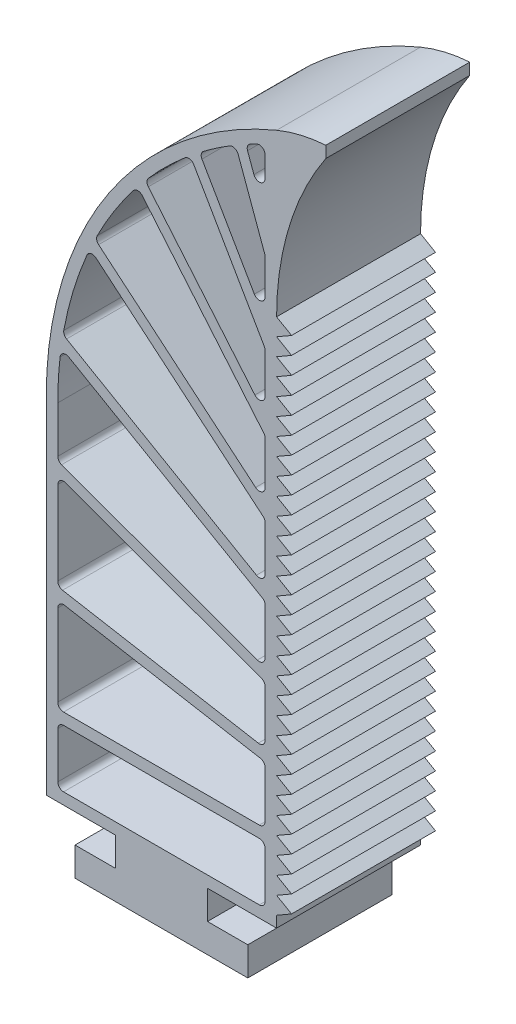
SolidWorks part; units mm, degrees
ref_plane "Front Plane" through (0, 0, 0) normal (0, 0, 1) x (1, 0, 0)
ref_plane "Top Plane" through (0, 0, 0) normal (0, 1, 0) x (1, 0, 0)
ref_plane "Right Plane" through (0, 0, 0) normal (1, 0, 0) x (0, 0, -1)
sketch "Sketch2" plane through (0, 0, 0) normal (0, 0, 1) x (1, 0, 0)
  line L0 (-15, 0) -> (15, 0)
  line L1 (15, 0) -> (15, 5)
  line L2 (15, 5) -> (8, 5)
  line L3 (8, 5) -> (8, 10)
  line L4 (8, 10) -> (20, 10)
  line L5 (20, 10) -> (20, 130)
  line L6 (-15, 0) -> (-15, 5)
  line L7 (-15, 5) -> (-8, 5)
  line L8 (-8, 5) -> (-8, 10)
  line L9 (-8, 10) -> (-20, 10)
  line L10 (-20, 10) -> (-20, 70)
  arc A0 (20, 130) -> (-20, 70) centre (45, 70) ccw
  dimension "D1" = 30
  dimension "D2" = 5
  dimension "D3" = 5
  dimension "D4" = 40
  dimension "D5" = 120
  dimension "D6" = 60
  dimension "D7" = 16
extrude "Boss-Extrude1" add sketch "Sketch2" along normal blind 25
sketch "Sketch3" plane through (0, 0, 25) normal (0, 0, 1) x (1, 0, 0)
  line L0 (-18, 12) -> (18, 12)
  line L1 (18, 12) -> (18, 22)
  line L2 (18, 22) -> (-18, 22)
  line L3 (-18, 22) -> (-18, 12)
  line L4 (-20, 70) -> (-20, 10) construction
  line L5 (20, 10) -> (20, 130) construction
  line L6 (8, 10) -> (20, 10) construction
  dimension "D1" = 2
  dimension "D2" = 2
  dimension "D3" = 2
  dimension "D4" = 10
sketch "Sketch4" plane through (0, 0, 25) normal (0, 0, 1) x (1, 0, 0)
  line L0 (-18, 24) -> (18, 24)
  line L1 (18, 24) -> (18, 34)
  line L2 (18, 34) -> (-18, 40.3478)
  line L3 (-18, 40.3478) -> (-18, 24)
  line L4 (-20, 70) -> (-20, 10) construction
  line L5 (18, 22) -> (-18, 22) construction
  line L6 (20, 10) -> (20, 130) construction
  dimension "D1" = 2
  dimension "D2" = 2
  dimension "D3" = 2
  dimension "D4" = 10
  dimension "D5" = 10
sketch "Sketch5" plane through (0, 0, 25) normal (0, 0, 1) x (1, 0, 0)
  line L0 (-18, 42.3786) -> (18, 36.0309)
  line L1 (18, 36.0309) -> (18, 46.0309)
  line L2 (18, 46.0309) -> (-18, 59.1338)
  line L3 (-18, 59.1338) -> (-18, 42.3786)
  line L4 (-20, 70) -> (-20, 10) construction
  line L5 (20, 10) -> (20, 130) construction
  line L7 (18, 34) -> (-18, 40.3478) construction
  line L8 (-18, 24) -> (18, 24) construction
  dimension "D1" = 2
  dimension "D2" = 2
  dimension "D3" = 2
  dimension "D4" = 20
  dimension "D5" = 10
sketch "Sketch6" plane through (0, 0, 25) normal (0, 0, 1) x (1, 0, 0)
  line L0 (-18, 61.2621) -> (18, 48.1592)
  line L1 (18, 48.1592) -> (18, 58.1592)
  line L2 (18, 58.1592) -> (-17.4098, 78.6031)
  line L3 (-18, 61.2621) -> (-18, 70)
  line L5 (18, 46.0309) -> (-18, 59.1338) construction
  line L6 (-20, 70) -> (-20, 10) construction
  line L7 (20, 10) -> (20, 130) construction
  line L8 (-18, 24) -> (18, 24) construction
  arc A0 (-17.4098, 78.6031) -> (-18, 70) centre (45, 70) ccw
  arc A2 (20, 130) -> (-20, 70) centre (45, 70) ccw construction
  dimension "D1" = 2
  dimension "D2" = 2
  dimension "D3" = 2
  dimension "D4" = 30
  dimension "D5" = 10
extrude "Cut-Extrude1" cut sketch "Sketch3" against normal through all contours L0 L1 L2 L3
extrude "Cut-Extrude2" cut sketch "Sketch4" against normal through all contours L0 L1 L2 L3
extrude "Cut-Extrude3" cut sketch "Sketch5" against normal through all contours L0 L1 L2 L3
extrude "Cut-Extrude4" cut sketch "Sketch6" against normal through all contours L0 L1 L2 A0 L3
sketch "Sketch13" plane through (0, 0, 25) normal (0, 0, 1) x (1, 0, 0)
  line L0 (20, 10) -> (20, 130) construction
  line L1 (28.5436, 132.0151) -> (28.5436, 130.0151)
  line L2 (20, 130) -> (20, 101.9347)
  arc A0 (20, 130) -> (28.5436, 132.0151) centre (30.3921, 105.059) cw
  arc A1 (20, 101.9347) -> (28.5436, 130.0151) centre (70.4182, 101.9347) cw
  arc A2 (20, 130) -> (-20, 70) centre (45, 70) ccw construction
  dimension "D1" = 2
extrude "Boss-Extrude2" add sketch "Sketch13" against normal up to surface (25 mm away) up to face at (-0.7569, 22.1713, 0)
sketch "Sketch15" plane through (0, 0, 25) normal (0, 0, 1) x (1, 0, 0)
  line L0 (20, 101.9347) -> (22.5981, 100.4347)
  line L1 (22.5981, 100.4347) -> (20, 98.9347)
  line L2 (20, 10) -> (20, 101.9347) construction
  line L3 (20, 101.9347) -> (20, 98.9347)
  dimension "D1" = 3
  dimension "D2" = 3
  dimension "D3" = 3
extrude "Boss-Extrude3" add sketch "Sketch15" against normal up to surface (25 mm away) up to face at (4.3889, 42.067, 0)
pattern_linear "LPattern1" count 30 spacing 3 along (0, -1, 0) of "Boss-Extrude3"
sketch "Sketch17" plane through (0, 0, 25) normal (0, 0, 1) x (1, 0, 0)
  line L0 (-17.0808, 80.7225) -> (18, 60.4686)
  line L1 (18, 60.4686) -> (18, 70.4686)
  line L2 (18, 70.4686) -> (-12.3964, 95.9742)
  line L3 (18, 58.1592) -> (-17.4098, 78.6031) construction
  line L4 (18, 48.1592) -> (18, 58.1592) construction
  arc A0 (-12.3964, 95.9742) -> (-17.0808, 80.7225) centre (45, 70) ccw
  arc A1 (-17.4098, 78.6031) -> (-18, 70) centre (45, 70) ccw construction
  dimension "D1" = 10
  dimension "D2" = 2
  dimension "D3" = 10
extrude "Cut-Extrude5" cut sketch "Sketch17" against normal through all contours L2 A0 L0 L1
sketch "Sketch18" plane through (0, 0, 25) normal (0, 0, 1) x (1, 0, 0)
  line L0 (-11.513, 97.8438) -> (18, 73.0794)
  line L1 (18, 73.0794) -> (18, 83.0794)
  line L2 (18, 83.0794) -> (-4.1233, 109.4449)
  line L3 (18, 70.4686) -> (-12.3964, 95.9742) construction
  line L4 (18, 60.4686) -> (18, 70.4686) construction
  arc A0 (-4.1233, 109.4449) -> (-11.513, 97.8438) centre (45, 70) ccw
  arc A1 (-12.3964, 95.9742) -> (-17.0808, 80.7225) centre (45, 70) ccw construction
  dimension "D1" = 2
  dimension "D2" = 10
  dimension "D3" = 10
extrude "Cut-Extrude6" cut sketch "Sketch18" against normal through all
sketch "Sketch19" plane through (0, 0, 25) normal (0, 0, 1) x (1, 0, 0)
  line L0 (-2.8251, 111.0093) -> (18, 86.1909)
  line L1 (18, 86.1909) -> (18, 96.1909)
  line L2 (18, 96.1909) -> (5.0138, 118.6837)
  line L3 (18, 73.0794) -> (18, 83.0794) construction
  line L5 (18, 83.0794) -> (-4.1233, 109.4449) construction
  arc A0 (5.0138, 118.6837) -> (-2.8251, 111.0093) centre (45, 70) ccw
  arc A1 (-4.1233, 109.4449) -> (-11.513, 97.8438) centre (45, 70) ccw construction
  dimension "D1" = 10
  dimension "D2" = 2
  dimension "D3" = 10
extrude "Cut-Extrude7" cut sketch "Sketch19" against normal through all contours L2 A0 L0 L1
sketch "Sketch21" plane through (0, 0, 25) normal (0, 0, 1) x (1, 0, 0)
  line L0 (6.5968, 119.9419) -> (18, 100.1909)
  line L1 (18, 100.1909) -> (18, 110.1909)
  line L2 (18, 110.1909) -> (12.8983, 124.2077)
  line L3 (18, 96.1909) -> (5.0138, 118.6837) construction
  line L4 (18, 86.1909) -> (18, 96.1909) construction
  arc A0 (12.8983, 124.2077) -> (6.5968, 119.9419) centre (45, 70) ccw
  arc A1 (5.0138, 118.6837) -> (-2.8251, 111.0093) centre (45, 70) ccw construction
  dimension "D1" = 10
  dimension "D2" = 2
  dimension "D3" = 10
extrude "Cut-Extrude8" cut sketch "Sketch21" against normal through all
sketch "Sketch22" plane through (0, 0, 25) normal (0, 0, 1) x (1, 0, 0)
  line L0 (14.6606, 125.2134) -> (18, 116.0385)
  line L1 (18, 116.0385) -> (18, 126.921)
  line L2 (18, 110.1909) -> (12.8983, 124.2077) construction
  line L3 (18, 100.1909) -> (18, 110.1909) construction
  arc A0 (18, 126.921) -> (14.6606, 125.2134) centre (45, 70) ccw
  arc A1 (12.8983, 124.2077) -> (6.5968, 119.9419) centre (45, 70) ccw construction
  dimension "D1" = 2
extrude "Cut-Extrude9" cut sketch "Sketch22" against normal through all
fillet "Fillet1" radius 1 35 edges at (18, 126.921, 12.5) (14.6606, 125.2134, 12.5) (6.5968, 119.9419, 12.5) (12.8983, 124.2077, 12.5) (18, 116.0385, 12.5) (18, 100.1909, 12.5) (-2.8251, 111.0093, 12.5) (5.0138, 118.6837, 12.5) (18, 86.1909, 12.5) (18, 73.0794, 12.5) (18, 60.4686, 12.5) (18, 46.0309, 12.5) (18, 22, 12.5) (18, 34, 12.5) (-18, 40.3478, 12.5) (-18, 22, 12.5) (-11.513, 97.8438, 12.5) (-17.0808, 80.7225, 12.5) (-18, 61.2621, 12.5) (-4.1233, 109.4449, 12.5) (-12.3964, 95.9742, 12.5) (-18, 59.1338, 12.5) (-17.4098, 78.6031, 12.5) (18, 96.1909, 12.5) (18, 110.1909, 12.5) (18, 83.0794, 12.5) (18, 70.4686, 12.5) (18, 58.1592, 12.5) (18, 48.1592, 12.5) (18, 36.0309, 12.5) (18, 12, 12.5) (18, 24, 12.5) (-18, 42.3786, 12.5) (-18, 24, 12.5) (-18, 12, 12.5)
